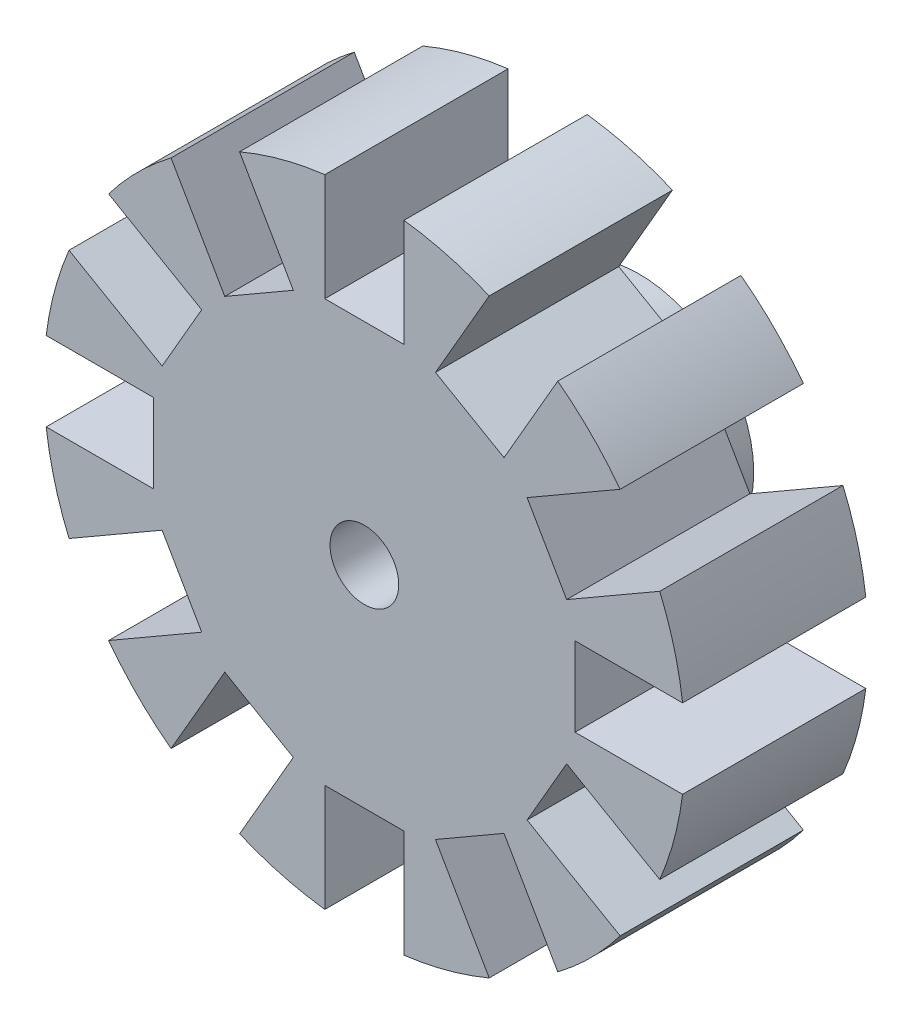
SolidWorks part; units mm, degrees
ref_plane "Front Plane" through (0, 0, 0) normal (0, 0, 1) x (1, 0, 0)
ref_plane "Top Plane" through (0, 0, 0) normal (0, 1, 0) x (1, 0, 0)
ref_plane "Right Plane" through (0, 0, 0) normal (1, 0, 0) x (0, 0, -1)
sketch "Sketch1" plane through (0, 0, 0) normal (0, 0, 1) x (1, 0, 0)
  circle A0 centre (0, 0) radius 14
  circle A1 centre (0, 0) radius 1.5
extrude "Boss-Extrude1" add sketch "Sketch1" along normal blind 8
ref_axis "Axis1" through (0, 0, -0.4) along (0, 0, 1)
sketch "Sketch2" plane through (0, 0, 0) normal (0, 0, 1) x (1, 0, 0)
  line L1 (9.2, -1.7279) -> (14.3, -1.7279)
  line L2 (9.2, -1.7279) -> (9.2, 1.7279)
  line L3 (9.2, 1.7279) -> (14.3, 1.7279)
  line L4 (14.3, -1.7279) -> (14.3, 1.7279)
extrude "Cut-Extrude2" cut sketch "Sketch2" along normal blind 9
pattern_circular "CirPattern1" count 12 every 30 about axis through (0, 0, -0.4) along (0, 0, 1) of "Cut-Extrude2"
sketch "Sketch3" plane through (0, 0, 0) normal (0, 0, 1) x (1, 0, 0)
  circle A0 centre (0, 0) radius 5
  circle A1 centre (0, 0) radius 1.5
extrude "Boss-Extrude2" add sketch "Sketch3" against normal blind 4
